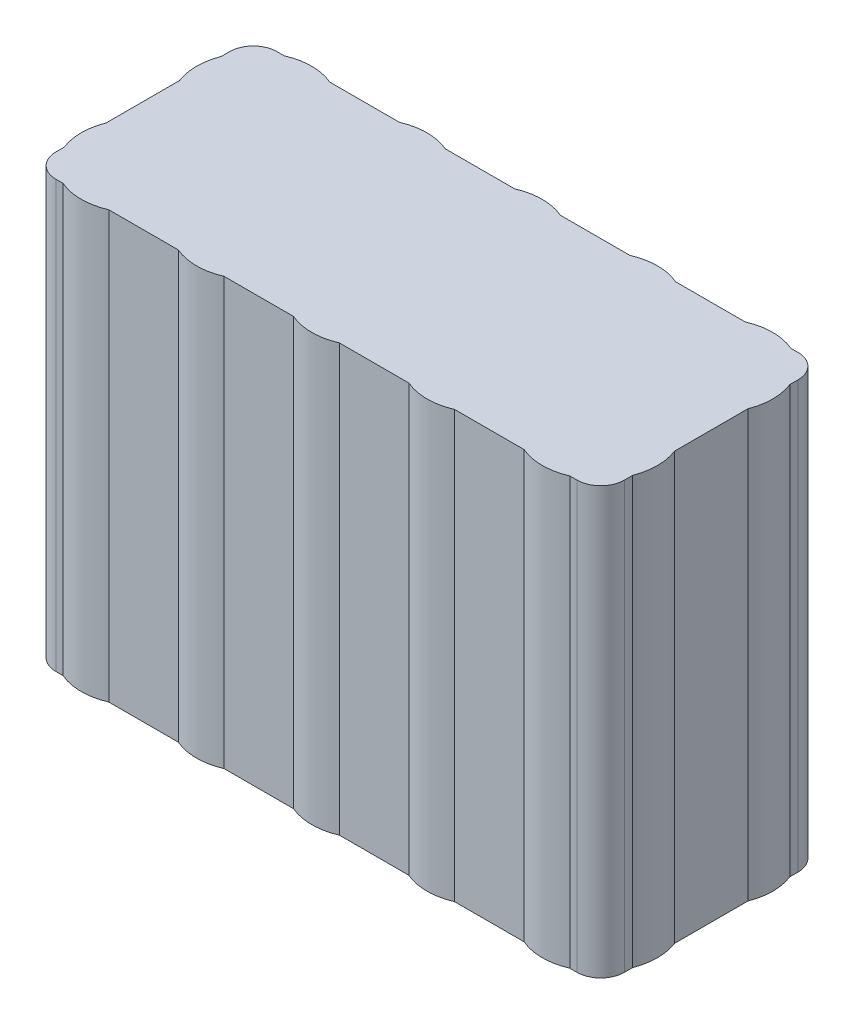
SolidWorks part; units mm, degrees
material "Gray Cast Iron"
ref_plane "Front" through (0, 0, 0) normal (0, 0, 1) x (1, 0, 0)
ref_plane "Top" through (0, 0, 0) normal (0, 1, 0) x (1, 0, 0)
ref_plane "Right" through (0, 0, 0) normal (1, 0, 0) x (0, 0, -1)
sketch "Sketch1" plane through (0, 0, 0) normal (0, 1, 0) x (1, 0, 0)
  line L0 (-27.8306, -10.7806) -> (30.5694, -10.7806) construction
  line L6 (-31.6306, -17.4806) -> (34.3694, -17.4806)
  line L7 (30.5694, -10.7806) -> (30.5694, 3.8194) construction
  line L8 (30.5694, 3.8194) -> (-27.8306, 3.8194) construction
  line L9 (-27.8306, 3.8194) -> (-27.8306, -10.7806) construction
  line L10 (-34.6306, -14.4806) -> (-34.6306, 7.5194)
  line L11 (-31.6306, 10.5194) -> (34.3694, 10.5194)
  line L12 (37.3694, -14.4806) -> (37.3694, 7.5194)
  line L13 (-34.6306, -17.4806) -> (37.3694, 10.5194) construction
  line L14 (-34.6306, 10.5194) -> (37.3694, -17.4806) construction
  circle A0 centre (-27.8306, -10.7806) radius 7.3
  circle A1 centre (-13.2306, -10.7806) radius 7.3
  circle A2 centre (1.3694, -10.7806) radius 7.3
  circle A3 centre (15.9694, -10.7806) radius 7.3
  circle A4 centre (30.5694, -10.7806) radius 7.3
  circle A5 centre (30.5694, 3.8194) radius 7.3
  circle A6 centre (-27.8306, 3.8194) radius 7.3
  circle A7 centre (-13.2306, 3.8194) radius 7.3
  circle A8 centre (1.3694, 3.8194) radius 7.3
  circle A9 centre (15.9694, 3.8194) radius 7.3
  arc A10 (-34.6306, -14.4806) -> (-31.6306, -17.4806) centre (-31.6306, -14.4806) ccw
  arc A11 (34.3694, -17.4806) -> (37.3694, -14.4806) centre (34.3694, -14.4806) ccw
  arc A12 (37.3694, 7.5194) -> (34.3694, 10.5194) centre (34.3694, 7.5194) ccw
  arc A13 (-34.6306, 7.5194) -> (-31.6306, 10.5194) centre (-31.6306, 7.5194) cw
  point P0 (0, 0)
  point P1 (1.3694, -3.4806)
  point P17 (0, 0)
  point P18 (0, 0)
  dimension "D3" = 14.6
  dimension "D13" = 72
  dimension "D14" = 3
  dimension "D15" = 3
  dimension "D16" = 3
  dimension "D17" = 3
  dimension "D2" = 28
  dimension "D4" = 14.6
  dimension "D5" = 14.6
  dimension "D6" = 14.6
  dimension "D7" = 14.6
  dimension "D8" = 14.6
  dimension "D9" = 14.6
  dimension "D10" = 14.6
  dimension "D11" = 14.6
  dimension "D12" = 14.6
extrude "Boss-Extrude1" add sketch "Sketch1" along normal blind 54 contours A6 L11 L10 | A13 L10 A6 L11 | A6 L10 A0 | A6 | L10 A13 L11 A12 L12 A11 L6 A10 | A0 | A1 | A2 | A3 | A4 | A5 | A9 | A8 | A7 region at (-33.056, 0, 3.4806) region at (-27.7542, 0, -3.7201) region at (-33.2827, 0, -9.1162)
